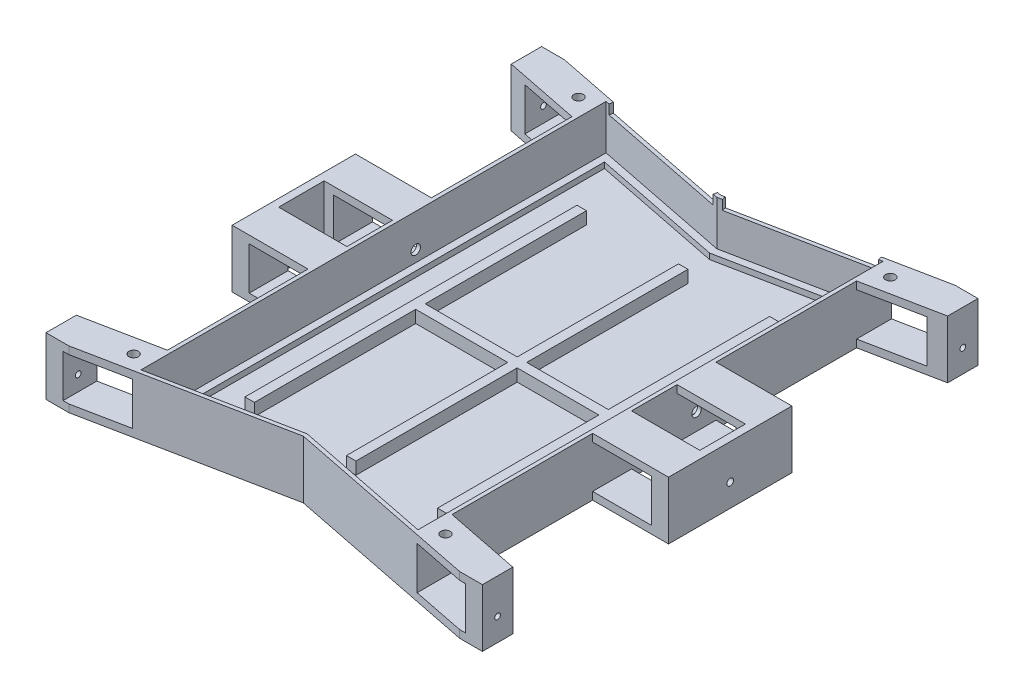
SolidWorks part; units mm, degrees
material "ABS"
ref_plane "Front Plane" through (0, 0, 0) normal (0, 0, 1) x (1, 0, 0)
ref_plane "Top Plane" through (0, 0, 0) normal (0, 1, 0) x (1, 0, 0)
ref_plane "Right Plane" through (0, 0, 0) normal (1, 0, 0) x (0, 0, -1)
sketch "Sketch1" plane through (0, 0, 0) normal (0, 1, 0) x (1, 0, 0)
  line L1 (-55, 0) -> (55, 0) construction
  line L2 (115, 32.5) -> (115, -32.5)
  line L3 (115, -32.5) -> (75, -32.5)
  line L4 (75, -32.5) -> (75, -106.6)
  line L5 (75, -106.6) -> (115, -114.6)
  line L6 (115, -114.6) -> (115, -130.6)
  line L7 (115, -130.6) -> (103, -130.6)
  line L8 (103, -130.6) -> (0, -110)
  line L9 (0, -55) -> (0, 55) construction
  line L11 (-115, 32.5) -> (-115, -32.5)
  line L12 (-115, -32.5) -> (-75, -32.5)
  line L13 (-75, -32.5) -> (-75, -106.6)
  line L14 (-75, -106.6) -> (-115, -114.6)
  line L15 (-115, -114.6) -> (-115, -130.6)
  line L16 (-115, -130.6) -> (-103, -130.6)
  line L17 (-103, -130.6) -> (0, -110)
  line L18 (115, 32.5) -> (75, 32.5)
  line L19 (75, 32.5) -> (75, 106.6)
  line L20 (115, 130.6) -> (103, 130.6)
  line L21 (115, 114.6) -> (115, 130.6)
  line L22 (75, 106.6) -> (115, 114.6)
  line L23 (103, 130.6) -> (0, 110)
  line L24 (-115, 114.6) -> (-115, 130.6)
  line L25 (-115, 130.6) -> (-103, 130.6)
  line L26 (-103, 130.6) -> (0, 110)
  line L27 (-75, 106.6) -> (-115, 114.6)
  line L28 (-115, 32.5) -> (-75, 32.5)
  line L29 (-75, 32.5) -> (-75, 106.6)
  line L30 (75, -106.6) -> (75, -125) construction
  line L32 (-75, -106.6) -> (-75, -125) construction
  line L34 (-75, 106.6) -> (-75, 125) construction
  line L36 (75, 106.6) -> (75, 125) construction
  point P21 (115, 0)
  point P33 (-115, 0)
  dimension "D1" = 250
  dimension "D2" = 220
  dimension "D3" = 150
  dimension "D4" = 16
  dimension "D5" = 12
  dimension "D6" = 65
  dimension "D7" = 40
extrude "Boss-Extrude1" add sketch "Sketch1" along normal blind 12 and the other way blind 12
sketch "Sketch2" plane through (0, 0, 130.6) normal (0, 0, 1) x (1, 0, 0)
  line L0 (-115, -12) -> (-115, 12) construction
  line L1 (-106, -8) -> (106, -8)
  line L2 (-106, -8) -> (-106, 8)
  line L3 (-106, 8) -> (106, 8)
  line L4 (106, -8) -> (106, 8)
  line L5 (115, -12) -> (115, 12) construction
  line L7 (55, 0) -> (-55, 0) construction
  dimension "D1" = 8
  dimension "D2" = 8
  dimension "D3" = 9
  dimension "D4" = 9
extrude "Cut-Extrude1" cut sketch "Sketch2" against normal blind 320
sketch "Sketch4" plane through (0, 12, 0) normal (0, 1, 0) x (1, 0, 0)
  line L0 (-55, 0) -> (55, 0) construction
  line L1 (-111, 12) -> (-75, 12)
  line L2 (-111, 12) -> (-111, -12)
  line L3 (-111, -12) -> (-75, -12)
  line L4 (-75, 12) -> (-75, -12)
  line L5 (-115, 32.5) -> (-115, -32.5) construction
  line L6 (-75, -32.5) -> (-75, -106.6) construction
  line L7 (0, -55) -> (0, 55) construction
  line L8 (111, -12) -> (75, -12)
  line L9 (75, 12) -> (75, -12)
  line L10 (111, 12) -> (75, 12)
  line L11 (111, 12) -> (111, -12)
  dimension "D1" = 12
  dimension "D2" = 12
  dimension "D3" = 4
extrude "Cut-Extrude2" cut sketch "Sketch4" against normal blind 24
sketch "Sketch6" plane through (0, 0, 0) normal (1, 0, 0) x (0, 0, -1)
  line L0 (-114.6, 0) -> (-130.6, 0) construction
  line L1 (114.6, 0) -> (130.6, 0) construction
  circle A0 centre (-122.6, 0) radius 1.5
  circle A1 centre (122.6, 0) radius 1.5
  point P6 (-122.6, 0)
  point P10 (122.6, 0)
  dimension "D1" = 3
extrude "Cut-Extrude3" cut sketch "Sketch6" against normal through all both and the other way through all
sketch "Sketch7" plane through (115, 0, 0) normal (1, 0, 0) x (0, 0, -1)
  circle A0 centre (0, 0) radius 1.75
  dimension "D1" = 3.5
extrude "Cut-Extrude4" cut sketch "Sketch7" against normal up to surface (230 mm away) up to face at (-115, 0, 0)
sketch "Sketch11" plane through (0, 12, 0) normal (0, 1, 0) x (1, 0, 0)
  line L0 (-75, -125) -> (-75, 125)
  line L1 (-103, -130.6) -> (0, -110) construction
  line L2 (0, 110) -> (-103, 130.6) construction
  line L3 (75, 125) -> (75, -125)
  line L4 (103, 130.6) -> (0, 110) construction
  line L5 (0, -110) -> (103, -130.6) construction
  line L6 (75, 32.5) -> (75, 106.6) construction
  line L7 (-75, 106.6) -> (-75, 32.5) construction
  line L8 (0, -110) -> (75, -125)
  line L9 (-75, -125) -> (0, -110)
  line L10 (0, 110) -> (-75, 125)
  line L11 (75, 125) -> (0, 110)
extrude "Cut-Extrude7" cut sketch "Sketch11" against normal up to surface (4 mm away) up to face at (0, 8, 0)
sketch "Sketch12" plane through (0, -8, 0) normal (0, 1, 0) x (1, 0, 0)
  line L0 (-75, 125) -> (-75, -125)
  line L1 (-103, -130.6) -> (0, -110) construction
  line L2 (75, 125) -> (75, -125)
  line L3 (-75, -125) -> (0, -110)
  line L4 (0, -110) -> (75, -125)
  line L5 (-75, 125) -> (0, 110)
  line L6 (0, 110) -> (75, 125)
  line L7 (0, 107.9604) -> (73, 122.5604)
  line L8 (73, 122.5604) -> (73, -122.5604)
  line L9 (0, -107.9604) -> (73, -122.5604)
  line L10 (-73, -122.5604) -> (0, -107.9604)
  line L11 (-73, 122.5604) -> (-73, -122.5604)
  line L12 (-73, 122.5604) -> (0, 107.9604)
  dimension "D1" = 2
extrude "Boss-Extrude2" add sketch "Sketch12" along normal blind 20
sketch "Sketch14" plane through (0, 12, 0) normal (0, 1, 0) x (1, 0, 0)
  line L0 (0, 110) -> (0, -110) construction
  line L1 (75, 0) -> (-75, 0) construction
  line L2 (75, -12) -> (75, 12) construction
  line L3 (-75, 12) -> (-75, -12) construction
  line L4 (-83.9461, 108.3892) -> (-80.4076, 126.0815) construction
  line L5 (-115, 114.6) -> (-75, 106.6) construction
  line L6 (0, 110) -> (-103, 130.6) construction
  circle A0 centre (-82.1768, 117.2354) radius 2.5
  circle A1 centre (82.1768, 117.2354) radius 2.5
  circle A2 centre (82.1768, -117.2354) radius 2.5
  circle A3 centre (-82.1768, -117.2354) radius 2.5
  dimension "D2" = 5
  dimension "D1" = 82
extrude "Cut-Extrude8" cut sketch "Sketch14" against normal up to next
sketch "Sketch15" plane through (0, 12, 0) normal (0, 1, 0) x (1, 0, 0)
  line L0 (-71.0388, 122.1682) -> (-70.6466, 124.1293)
  line L1 (0, 110) -> (-103, 130.6) construction
  line L2 (0, 107.9604) -> (-73, 122.5604) construction
  line L3 (-2.3982, 108.44) -> (-71.0388, 122.1682)
  line L4 (-2.006, 110.4012) -> (-70.6466, 124.1293)
  line L5 (73, 122.5604) -> (0, 107.9604) construction
  line L6 (103, 130.6) -> (0, 110) construction
  line L7 (71.0388, 122.1682) -> (2.3982, 108.44)
  line L8 (70.6466, 124.1293) -> (2.006, 110.4012)
  line L10 (-2.3982, 108.44) -> (-2.006, 110.4012)
  line L11 (2.3982, 108.44) -> (2.006, 110.4012)
  line L12 (70.6466, 124.1293) -> (71.0388, 122.1682)
  dimension "D1" = 70
  dimension "D2" = 70
  dimension "D3" = 2
  dimension "D4" = 2
extrude "Cut-Extrude9" cut sketch "Sketch15" against normal blind 5
sketch "Sketch16" plane through (75, 0, 0) normal (1, 0, 0) x (0, 0, -1)
  line L0 (22.25, 8) -> (22.25, -8) construction
  line L1 (32.5, 8) -> (12, 8) construction
  line L2 (12, -8) -> (32.5, -8) construction
  circle A0 centre (22.25, 1) radius 2.5
  dimension "D2" = 5
  dimension "D1" = 9
extrude "Cut-Extrude10" cut sketch "Sketch16" against normal up to surface (150 mm away) up to face at (-75, 0, 0)
sketch "Sketch17" plane through (0, 12, 0) normal (0, 1, 0) x (1, 0, 0)
  line L0 (-75, 12) -> (-75, -12) construction
  line L1 (-111, -12) -> (-75, -12) construction
  line L2 (-111, 12) -> (-111, -12) construction
  line L3 (-75, 12) -> (-111, 12) construction
  line L4 (-75, 12) -> (-75, -12)
  line L5 (-111, -12) -> (-75, -12)
  line L6 (-2.006, 110.4012) -> (-2.3982, 108.44)
  line L7 (-2.3982, 108.44) -> (0, 107.9604)
  line L8 (0, 107.9604) -> (2.3982, 108.44)
  line L9 (2.3982, 108.44) -> (2.006, 110.4012)
  line L10 (2.006, 110.4012) -> (0, 110)
  line L11 (0, 110) -> (-2.006, 110.4012)
  line L12 (-2.006, 110.4012) -> (-2.3982, 108.44)
  line L13 (-2.3982, 108.44) -> (0, 107.9604)
  line L14 (0, 107.9604) -> (2.3982, 108.44)
  line L15 (2.3982, 108.44) -> (2.006, 110.4012)
  line L16 (2.006, 110.4012) -> (0, 110)
  line L17 (0, 110) -> (-2.006, 110.4012)
  line L18 (-111, 12) -> (-111, -12)
  line L19 (-75, 12) -> (-111, 12)
  line L20 (111, 12) -> (75, 12) construction
  line L21 (111, -12) -> (111, 12) construction
  line L22 (75, -12) -> (111, -12) construction
  line L23 (75, -12) -> (75, 12) construction
  line L24 (75, -12) -> (75, 12)
  line L25 (75, -12) -> (111, -12)
  line L26 (111, -12) -> (111, 12)
  line L27 (111, 12) -> (75, 12)
  line L34 (-71.0388, 122.1682) -> (-70.6466, 124.1293)
  line L35 (-70.6466, 124.1293) -> (-103, 130.6)
  line L36 (-103, 130.6) -> (-115, 130.6)
  line L37 (-115, 130.6) -> (-115, 114.6)
  line L38 (-115, 114.6) -> (-75, 106.6)
  line L39 (-75, 106.6) -> (-75, 32.5)
  line L40 (-75, 32.5) -> (-115, 32.5)
  line L41 (-115, 32.5) -> (-115, -32.5)
  line L42 (-115, -32.5) -> (-75, -32.5)
  line L43 (-75, -32.5) -> (-75, -106.6)
  line L44 (-75, -106.6) -> (-115, -114.6)
  line L45 (-115, -114.6) -> (-115, -130.6)
  line L46 (-115, -130.6) -> (-103, -130.6)
  line L47 (-103, -130.6) -> (0, -110)
  line L48 (0, -110) -> (103, -130.6)
  line L49 (103, -130.6) -> (115, -130.6)
  line L50 (115, -130.6) -> (115, -114.6)
  line L51 (115, -114.6) -> (75, -106.6)
  line L52 (75, -106.6) -> (75, -32.5)
  line L53 (75, -32.5) -> (115, -32.5)
  line L54 (115, -32.5) -> (115, 32.5)
  line L55 (115, 32.5) -> (75, 32.5)
  line L56 (75, 32.5) -> (75, 106.6)
  line L57 (75, 106.6) -> (115, 114.6)
  line L58 (115, 114.6) -> (115, 130.6)
  line L59 (115, 130.6) -> (103, 130.6)
  line L60 (103, 130.6) -> (70.6466, 124.1293)
  line L61 (70.6466, 124.1293) -> (71.0388, 122.1682)
  line L62 (71.0388, 122.1682) -> (73, 122.5604)
  line L63 (73, 122.5604) -> (73, -122.5604)
  line L64 (73, -122.5604) -> (0, -107.9604)
  line L65 (0, -107.9604) -> (-73, -122.5604)
  line L66 (-73, -122.5604) -> (-73, 122.5604)
  line L67 (-73, 122.5604) -> (-71.0388, 122.1682)
  line L68 (-71.0388, 122.1682) -> (-70.6466, 124.1293)
  line L69 (-70.6466, 124.1293) -> (-103, 130.6)
  line L70 (-103, 130.6) -> (-115, 130.6)
  line L71 (-115, 130.6) -> (-115, 114.6)
  line L72 (-115, 114.6) -> (-75, 106.6)
  line L73 (-75, 106.6) -> (-75, 32.5)
  line L74 (-75, 32.5) -> (-115, 32.5)
  line L75 (-115, 32.5) -> (-115, -32.5)
  line L76 (-115, -32.5) -> (-75, -32.5)
  line L77 (-75, -32.5) -> (-75, -106.6)
  line L78 (-75, -106.6) -> (-115, -114.6)
  line L79 (-115, -114.6) -> (-115, -130.6)
  line L80 (-115, -130.6) -> (-103, -130.6)
  line L81 (-103, -130.6) -> (0, -110)
  line L82 (0, -110) -> (103, -130.6)
  line L83 (103, -130.6) -> (115, -130.6)
  line L84 (115, -130.6) -> (115, -114.6)
  line L85 (115, -114.6) -> (75, -106.6)
  line L86 (75, -106.6) -> (75, -32.5)
  line L87 (75, -32.5) -> (115, -32.5)
  line L88 (115, -32.5) -> (115, 32.5)
  line L89 (115, 32.5) -> (75, 32.5)
  line L90 (75, 32.5) -> (75, 106.6)
  line L91 (75, 106.6) -> (115, 114.6)
  line L92 (115, 114.6) -> (115, 130.6)
  line L93 (115, 130.6) -> (103, 130.6)
  line L94 (103, 130.6) -> (70.6466, 124.1293)
  line L95 (70.6466, 124.1293) -> (71.0388, 122.1682)
  line L96 (71.0388, 122.1682) -> (73, 122.5604)
  line L97 (73, 122.5604) -> (73, -122.5604)
  line L98 (73, -122.5604) -> (0, -107.9604)
  line L99 (0, -107.9604) -> (-73, -122.5604)
  line L100 (-73, -122.5604) -> (-73, 122.5604)
  line L101 (-73, 122.5604) -> (-71.0388, 122.1682)
  circle A0 centre (82.1768, -117.2354) radius 2.5 construction
  circle A1 centre (-82.1768, -117.2354) radius 2.5 construction
  circle A2 centre (-82.1768, 117.2354) radius 2.5 construction
  circle A3 centre (82.1768, 117.2354) radius 2.5 construction
  circle A4 centre (82.1768, -117.2354) radius 2.5
  circle A5 centre (-82.1768, -117.2354) radius 2.5
  circle A6 centre (-82.1768, 117.2354) radius 2.5
  circle A7 centre (82.1768, 117.2354) radius 2.5
  dimension "D1" = 0
  dimension "D2" = 0
extrude "Boss-Extrude3" add sketch "Sketch17" along normal blind 6.5
sketch "Sketch18" plane through (0, 7, 0) normal (0, 1, 0) x (1, 0, 0)
  line L0 (-71.0388, 122.1682) -> (-2.3982, 108.44) construction
  line L1 (-2.3982, 108.44) -> (-2.006, 110.4012) construction
  line L2 (-2.006, 110.4012) -> (-70.6466, 124.1293) construction
  line L3 (-70.6466, 124.1293) -> (-71.0388, 122.1682) construction
  line L4 (71.0388, 122.1682) -> (70.6466, 124.1293) construction
  line L5 (70.6466, 124.1293) -> (2.006, 110.4012) construction
  line L6 (2.006, 110.4012) -> (2.3982, 108.44) construction
  line L7 (2.3982, 108.44) -> (71.0388, 122.1682) construction
  line L8 (-71.0388, 122.1682) -> (-2.3982, 108.44)
  line L9 (-2.3982, 108.44) -> (-2.006, 110.4012)
  line L10 (-2.006, 110.4012) -> (-70.6466, 124.1293)
  line L11 (-70.6466, 124.1293) -> (-71.0388, 122.1682)
  line L12 (71.0388, 122.1682) -> (70.6466, 124.1293)
  line L13 (70.6466, 124.1293) -> (2.006, 110.4012)
  line L14 (2.006, 110.4012) -> (2.3982, 108.44)
  line L15 (2.3982, 108.44) -> (71.0388, 122.1682)
extrude "Boss-Extrude4" add sketch "Sketch18" along normal blind 6.5
sketch "Sketch19" plane through (0, 0, -130.6) normal (0, 0, -1) x (-1, 0, 0)
  line L0 (0, -12) -> (0, 18.5) construction
  line L1 (-106, 8) -> (-75, 8)
  line L2 (-75, 8) -> (-75, 14.5)
  line L3 (-75, 14.5) -> (-106, 14.5)
  line L4 (-106, 14.5) -> (-106, 8)
  line L6 (-103, 18.5) -> (-70.6466, 18.5) construction
  line L7 (75, 14.5) -> (106, 14.5)
  line L8 (75, 8) -> (75, 14.5)
  line L9 (106, 8) -> (75, 8)
  line L10 (106, 14.5) -> (106, 8)
  dimension "D1" = 4
extrude "Cut-Extrude11" cut sketch "Sketch19" against normal through all
sketch "Sketch20" plane through (0, -8, 0) normal (0, 1, 0) x (1, 0, 0)
  line L0 (69.25, 117.9861) -> (0, 104.1361)
  line L1 (0, 104.1361) -> (-69.25, 117.9861)
  line L2 (-69.25, 117.9861) -> (-69.25, -117.9861)
  line L3 (-69.25, -117.9861) -> (0, -104.1361)
  line L4 (0, -104.1361) -> (69.25, -117.9861)
  line L5 (69.25, -117.9861) -> (69.25, 117.9861)
  line L6 (73, 122.5604) -> (0, 107.9604)
  line L7 (0, 107.9604) -> (-73, 122.5604)
  line L8 (-73, 122.5604) -> (-73, -122.5604)
  line L9 (-73, -122.5604) -> (0, -107.9604)
  line L10 (0, -107.9604) -> (73, -122.5604)
  line L11 (73, -122.5604) -> (73, 122.5604)
  line L12 (73, 122.5604) -> (0, 107.9604)
  line L13 (0, 107.9604) -> (-73, 122.5604)
  line L14 (-73, 122.5604) -> (-73, -122.5604)
  line L15 (-73, -122.5604) -> (0, -107.9604)
  line L16 (0, -107.9604) -> (73, -122.5604)
  line L17 (73, -122.5604) -> (73, 122.5604)
  dimension "D1" = 0
  dimension "D2" = 3.75
extrude "Boss-Extrude5" add sketch "Sketch20" along normal blind 3
sketch "Sketch21" plane through (0, -8, 0) normal (0, 1, 0) x (1, 0, 0)
  line L3 (5.25, -2.5) -> (5.25, -87.5)
  line L4 (5.25, -87.5) -> (0.25, -87.5)
  line L5 (0.25, -87.5) -> (0.25, -2.5)
  line L9 (0.25, 2.5) -> (0.25, 87.5)
  line L10 (0.25, 87.5) -> (5.25, 87.5)
  line L11 (5.25, 87.5) -> (5.25, 2.5)
  line L12 (0.25, 2.5) -> (-48.25, 2.5)
  line L13 (-48.25, 2.5) -> (-48.25, -2.5) construction
  line L14 (53.25, -87.5) -> (53.25, 87.5)
  line L15 (53.25, 87.5) -> (48.25, 87.5)
  line L16 (48.25, 87.5) -> (48.25, 2.5)
  line L17 (5.25, 2.5) -> (48.25, 2.5)
  line L18 (5.25, -2.5) -> (48.25, -2.5)
  line L19 (48.25, -2.5) -> (48.25, -87.5)
  line L20 (48.25, -87.5) -> (53.25, -87.5)
  line L21 (69.25, -117.9861) -> (69.25, 117.9861) construction
  line L22 (-48.25, 2.5) -> (-48.25, 87.5)
  line L23 (-48.25, 87.5) -> (-53.25, 87.5)
  line L24 (-53.25, 87.5) -> (-53.25, -87.5)
  line L25 (-53.25, -87.5) -> (-48.25, -87.5)
  line L26 (-48.25, -87.5) -> (-48.25, -2.5)
  line L27 (-48.25, -2.5) -> (0.25, -2.5)
  line L28 (-69.25, 117.9861) -> (-69.25, -117.9861) construction
  line L29 (48.25, 2.5) -> (48.25, -2.5) construction
  line L30 (48.25, 0) -> (-48.25, 0) construction
  dimension "D1" = 16
  dimension "D2" = 5
  dimension "D3" = 16
  dimension "D4" = 48.5
  dimension "D5" = 5
  dimension "D6" = 175
extrude "Boss-Extrude6" add sketch "Sketch21" along normal blind 6.5
equation "\"A\"= 4"
equation "\"D1@Boss-Extrude1\"=3*\"A\""
equation "\"D2@Boss-Extrude1\"=3*\"A\""
equation "\"D1@Sketch2\"=2*\"A\""
equation "\"D2@Sketch2\"=2*\"A\""
equation "\"D1@Sketch4\"=3*\"A\""
equation "\"D2@Sketch4\"=3*\"A\""
equation "\"D3@Sketch4\"=\"A\""
equation "\"D1@Cut-Extrude2\"=6*\"A\""
equation "\"D1@Cut-Extrude1\"=80*\"A\""
